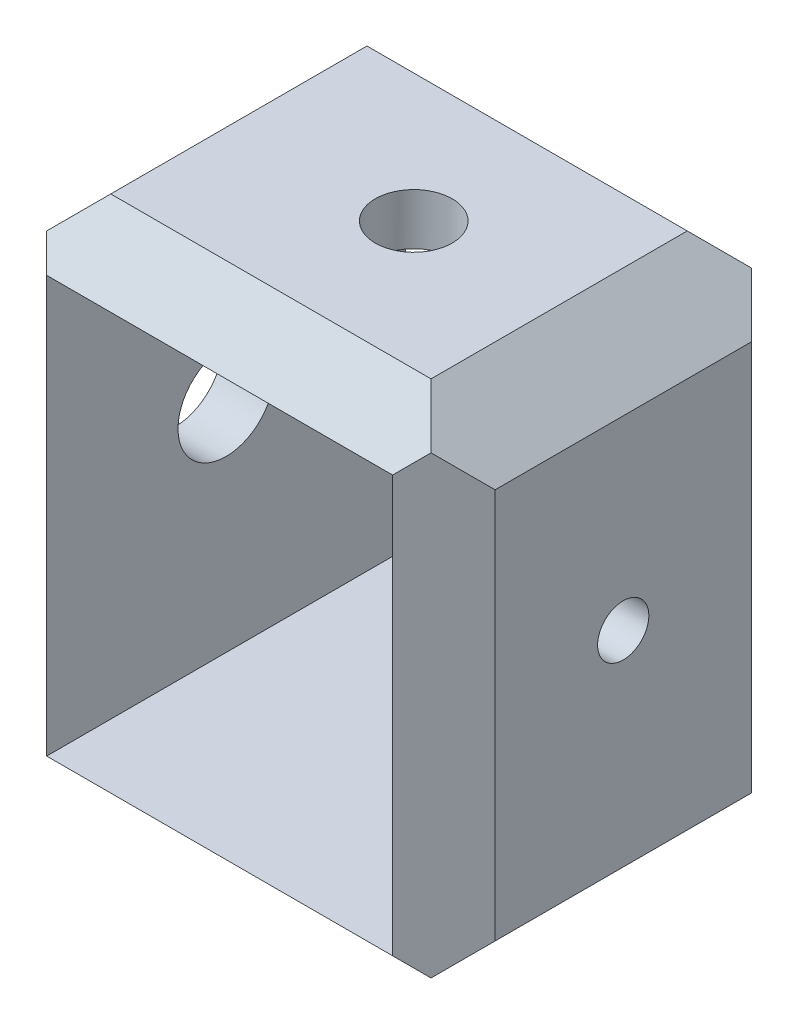
SolidWorks part; units mm, degrees
ref_plane "Front Plane" through (0, 0, 0) normal (0, 0, 1) x (1, 0, 0)
ref_plane "Top Plane" through (0, 0, 0) normal (0, 1, 0) x (1, 0, 0)
ref_plane "Right Plane" through (0, 0, 0) normal (1, 0, 0) x (0, 0, -1)
sketch "Sketch1" plane through (0, 0, 0) normal (0, 0, 1) x (1, 0, 0)
  line L5 (-259.8971, 0) -> (296.333, 0) construction
  line L6 (-132.6077, 195) -> (217.3923, 195)
  line L10 (-132.6077, 195) -> (-132.6077, -210)
  line L11 (-132.6077, -210) -> (217.3923, -210)
  line L12 (217.3923, 195) -> (217.3923, -210)
  line L13 (-92.6077, 155) -> (-92.6077, -170)
  line L14 (-92.6077, -170) -> (177.3923, -170)
  line L15 (177.3923, 155) -> (177.3923, -170)
  line L16 (-92.6077, 155) -> (177.3923, 155)
  dimension "D1" = 405
  dimension "D2" = 350
  dimension "D4" = 40
  dimension "D3" = 170
extrude "Boss-Extrude1" add sketch "Sketch1" along normal mid plane 300
sketch "Sketch2" plane through (-132.6077, 0, 0) normal (-1, 0, 0) x (0, 0, 1)
  circle A0 centre (0, 0) radius 37.5
  dimension "D1" = 75
extrude "Cut-Extrude1" cut sketch "Sketch2" against normal up to surface (40 mm away) up to face at (-92.6077, -7.5, 0)
sketch "Sketch3" plane through (217.3923, 0, 0) normal (1, 0, 0) x (0, 0, -1)
  circle A0 centre (0, 0) radius 20
  dimension "D1" = 40
extrude "Cut-Extrude2" cut sketch "Sketch3" against normal up to surface (40 mm away) up to face at (177.3923, -7.5, 0)
sketch "Sketch4" plane through (0, 195, 0) normal (0, 1, 0) x (1, 0, 0)
  line L0 (-132.6077, -150) -> (-132.6077, 150) construction
  circle A1 centre (53.8823, 0) radius 30
  point P6 (-132.6077, 0)
  dimension "D1" = 60
  dimension "D2" = 186.49
extrude "Cut-Extrude3" cut sketch "Sketch4" against normal up to surface (40 mm away) up to face at (42.3923, 155, 0)
chamfer "Chamfer1" distance 50 angle 45 4 edges at (217.3923, -210, 0) (-132.6077, -210, 0) (217.3923, 195, 0) (-132.6077, 195, 0)
chamfer "Chamfer2" distance 50 angle 45 4 edges at (42.3923, -210, -150) (42.3923, 195, -150) (42.3923, 195, 150) (42.3923, -210, 150)
chamfer "Chamfer3" distance 50 angle 45 4 edges at (217.3923, -7.5, 150) (-132.6077, -7.5, 150) (-132.6077, -7.5, -150) (217.3923, -7.5, -150)
